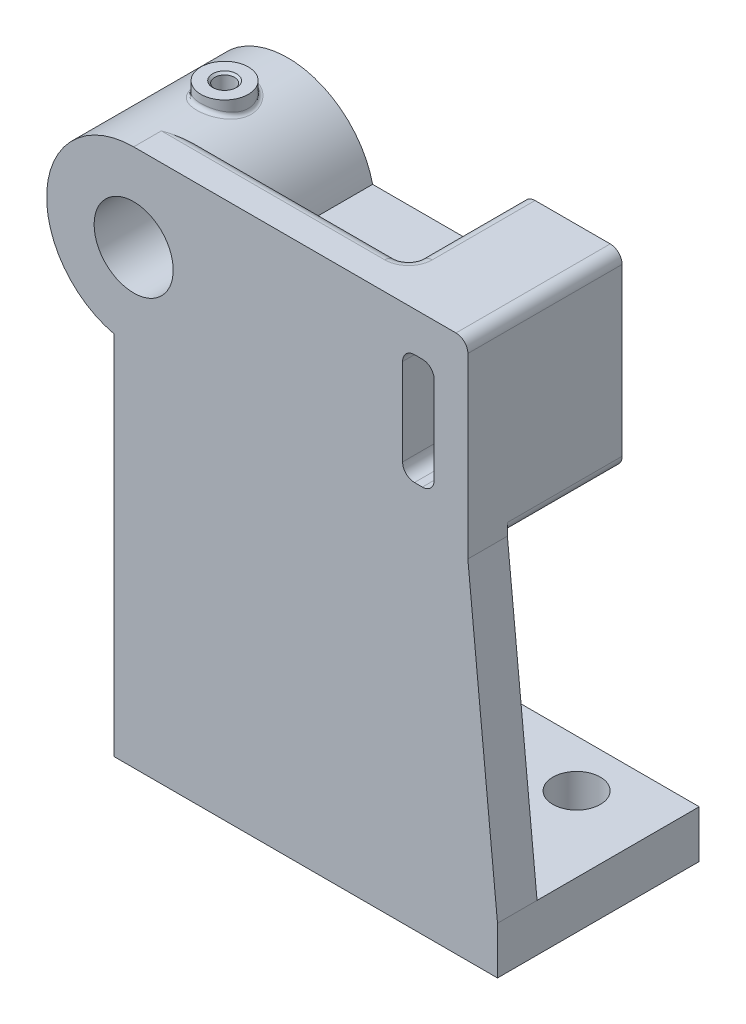
SolidWorks part; units mm, degrees
ref_plane "Front Plane" through (0, 0, 0) normal (0, 0, 1) x (1, 0, 0)
ref_plane "Top Plane" through (0, 0, 0) normal (0, 1, 0) x (1, 0, 0)
ref_plane "Right Plane" through (0, 0, 0) normal (1, 0, 0) x (0, 0, -1)
sketch "Sketch1" plane through (0, 0, 0) normal (0, 0, 1) x (1, 0, 0)
  line L1 (0, 0) -> (92, 0)
  line L2 (0, 0) -> (0, 12)
  line L3 (0, 12) -> (92, 12)
  line L4 (92, 0) -> (92, 12)
  dimension "D1" = 92
  dimension "D2" = 12
extrude "Boss-Extrude1" add sketch "Sketch1" along normal blind 51
sketch "Sketch9" plane through (0, 0, 51) normal (0, 0, 1) x (1, 0, 0)
  line L0 (0, 0) -> (92, 0) construction
  line L3 (84.5, 136) -> (59.5, 136)
  line L4 (84.5, 136) -> (84.5, 88)
  line L5 (84.5, 88) -> (59.5, 88)
  line L6 (59.5, 136) -> (59.5, 88)
  line L7 (84.5, 136) -> (59.5, 88) construction
  line L8 (84.5, 88) -> (59.5, 136) construction
  line L9 (76, 126) -> (68, 126)
  line L10 (76, 126) -> (76, 98)
  line L11 (76, 98) -> (68, 98)
  line L12 (68, 126) -> (68, 98)
  line L13 (76, 126) -> (68, 98) construction
  line L14 (76, 98) -> (68, 126) construction
  circle A0 centre (0, 114) radius 22
  point P4 (72, 112)
  point P10 (72, 112)
  point P15 (56.945, 105.7853)
  dimension "D2" = 44
  dimension "D1" = 114
  dimension "D3" = 25
  dimension "D4" = 28
  dimension "D5" = 8
  dimension "D6" = 48
  dimension "D7" = 20
extrude "Boss-Extrude4" add sketch "Sketch9" against normal blind 39 separate body
sketch "Sketch10" plane through (0, 0, 0) normal (-1, 0, 0) x (0, 0, 1)
  line L0 (0, 0) -> (0, 12)
  line L1 (0, 12) -> (12, 88)
  line L2 (12, 88) -> (12, 94)
  line L3 (12, 136) -> (12, 92) construction
  line L4 (12, 94) -> (51, 94)
  line L5 (51, 92) -> (51, 136) construction
  line L6 (51, 94) -> (51, 88)
  line L7 (51, 88) -> (51, 12)
  line L8 (51, 12) -> (51, 0)
  line L9 (51, 0) -> (0, 0)
  dimension "D1" = 94
extrude "Boss-Extrude5" add sketch "Sketch10" against normal mid plane 10
hole_wizard "Hole2" positions "Sketch11" profile "Sketch12" legacy end condition up to next
sketch "Sketch11" plane through (0, 0, 12) normal (0, 0, -1) x (-1, 0, 0)
  point P0 (0, 114)
sketch "Sketch12" plane through (0, 114, 12) normal (1, 0, 0) x (0, 1, 0)
  line L0 (0, 0) -> (0, 39.001)
  line L1 (0, 39.001) -> (10, 39.001)
  line L2 (10, 39.001) -> (10, 5)
  line L3 (10, 5) -> (16, 5)
  line L4 (16, 5) -> (16, 0)
  line L5 (16, 0) -> (0, 0)
  line L6 (0, 110) -> (0, -10) construction
  dimension "Diameter" = 20
  dimension "Depth" = 39.001
  dimension "C-Bore Diameter" = 32
  dimension "C-Bore Depth" = 5
sketch "Sketch13" plane through (0, 0, 51) normal (0, 0, 1) x (1, 0, 0)
  line L0 (92, 12) -> (5, 12) construction
  line L1 (5, 12) -> (5, 92.5757) construction
  line L2 (59.5, 136) -> (59.5, 88) construction
  line L3 (92, 12) -> (5, 12)
  line L4 (5, 12) -> (5, 92.5757)
  line L5 (59.5, 136) -> (59.5, 88)
  line L6 (0, 136) -> (59.5, 136)
  line L8 (59.5, 88) -> (84.5, 88)
  line L9 (84.5, 88) -> (92, 12)
  arc A0 (5, 92.5757) -> (-5, 92.5757) centre (0, 114) ccw construction
  arc A1 (5, 92.5757) -> (0, 136) centre (0, 114) ccw
extrude "Boss-Extrude6" add sketch "Sketch13" against normal blind 10
sketch "Sketch14" plane through (0, 0, 12) normal (0, 0, -1) x (-1, 0, 0)
  line L0 (-59.5, 136) -> (-59.5, 88) construction
  line L1 (-59.5, 119) -> (-59.5, 109)
  line L2 (-59.5, 119) -> (-21.4243, 119)
  line L3 (0, 114) -> (-64.5485, 114) construction
  line L4 (-59.5, 109) -> (-21.4243, 109)
  arc A0 (5, 92.5757) -> (-5, 92.5757) centre (0, 114) ccw construction
  arc A1 (-21.4243, 119) -> (-21.4243, 109) centre (0, 114) ccw
  dimension "D1" = 10
extrude "Boss-Extrude7" add sketch "Sketch14" against normal up to surface (29 mm away) up to face at (46.4079, 80.9721, 41)
ref_plane "Plane1" through (0, 139, 0) normal (0, 1, 0) x (1, 0, 0)
sketch "Sketch15" plane through (0, 139, 0) normal (0, 1, 0) x (1, 0, 0)
  line L0 (92, -41) -> (92, 0) construction
  line L1 (5, -12) -> (-5, -12) construction
  circle A0 centre (0, -28) radius 6
  dimension "D1" = 12
  dimension "D2" = 92
  dimension "D3" = 16
extrude "Boss-Extrude8" add sketch "Sketch15" against normal up to next
hole_wizard "M6 Tapped Hole1" positions "Sketch16" profile "Sketch17" tap size "M6" standard "ISO" end condition up to next
sketch "Sketch16" plane through (0, 139, 0) normal (0, 1, 0) x (1, 0, 0)
  point P0 (0, -28)
sketch "Sketch17" plane through (0, 139, 28) normal (1, 0, 0) x (0, 0, 1)
  line L0 (0, 0) -> (0, 15)
  line L1 (0, 15) -> (2.5, 15)
  line L2 (2.5, 15) -> (2.5, 0.525)
  line L3 (2.5, 0.525) -> (3.025, 0)
  line L5 (3.025, 0) -> (0, 0)
  line L6 (-2.5, 0.525) -> (-3.025, 0) construction
  line L11 (0, -6.35) -> (0, 107.95) construction
  dimension "Thru Tap Drill Dia." = 5
  dimension "Thru Tap Drill Depth" = 15
  dimension "Near C'Sink Dia." = 6.05
  dimension "Near C'Sink Angle" = 90
cosmetic thread "Hole Thread1" parameters "D2"=6
fillet "Fillet1" radius 3 4 edges at (29.75, 136, 41) (59.5, 88, 26.5) (59.5, 127.5, 41) (59.5, 136, 26.5)
fillet "Fillet2" radius 3 4 edges at (76, 126, 31.5) (68, 126, 31.5) (68, 98, 31.5) (76, 98, 31.5)
fillet "Fillet3" radius 3 2 edges at (84.5, 88, 26.5) (84.5, 136, 31.5)
fillet "Fillet4" radius 1 1 edges at (-1.1354, 135.9707, 22.1084)
hole_wizard "Hole3" positions "Sketch18" profile "Sketch19" legacy end condition up to next
sketch "Sketch18" plane through (0, 12, 0) normal (0, 1, 0) x (1, 0, 0)
  line L0 (92, -41) -> (92, 0) construction
  line L1 (92, 0) -> (5, 0) construction
  point P0 (73, -12)
  dimension "D1" = 19
  dimension "D2" = 12
sketch "Sketch19" plane through (73, 12, 12) normal (1, 0, 0) x (0, 0, 1)
  line L0 (0, 0) -> (0, 12)
  line L1 (0, 12) -> (6, 12)
  line L2 (6, 12) -> (6, 0)
  line L3 (6, 0) -> (0, 0)
  line L4 (0, 110) -> (0, -10) construction
  dimension "Diameter" = 12
  dimension "Depth" = 12
pattern_linear "LPattern1" count 2 spacing 44 along (-1, 0, 0) of "Hole3"
